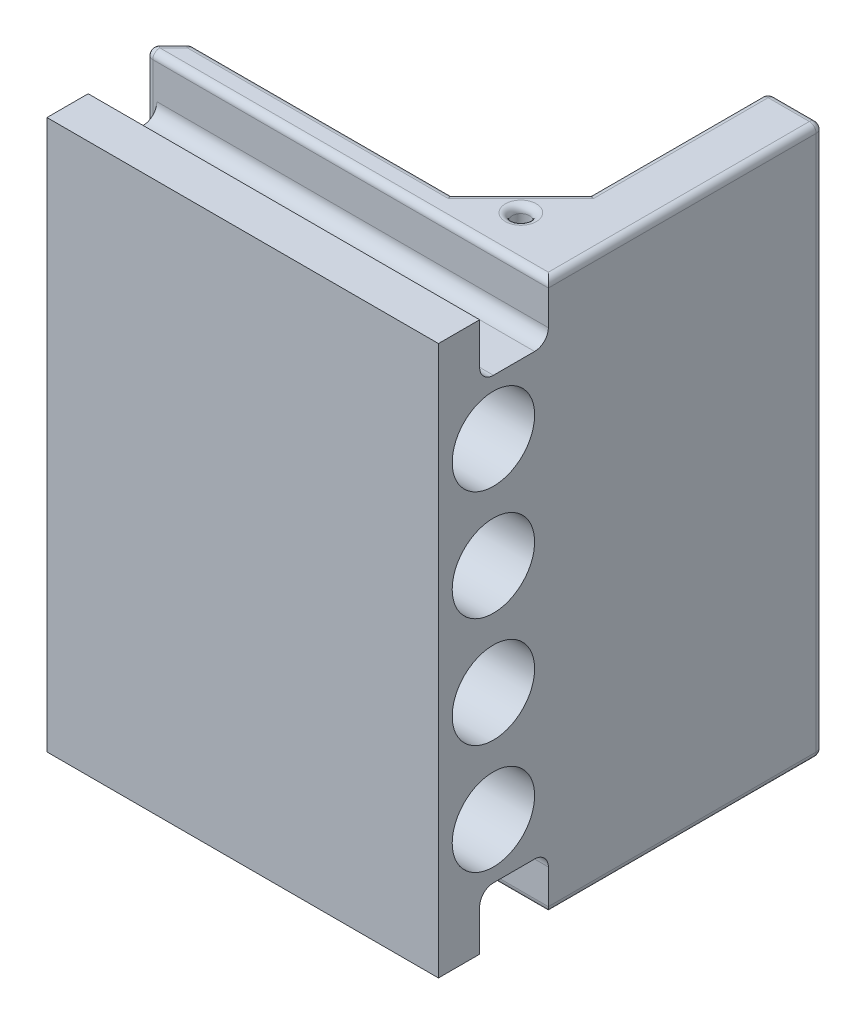
SolidWorks part; units mm, degrees
ref_plane "Front Plane" through (0, 0, 0) normal (0, 0, 1) x (1, 0, 0)
ref_plane "Top Plane" through (0, 0, 0) normal (0, 1, 0) x (1, 0, 0)
ref_plane "Right Plane" through (0, 0, 0) normal (1, 0, 0) x (0, 0, -1)
sketch "Sketch1" plane through (0, 0, 0) normal (0, 1, 0) x (1, 0, 0)
  line L0 (-17.3516, 20.3127) -> (-57.3516, -19.6873)
  line L1 (-17.3516, 20.3127) -> (2.6484, 20.3127)
  line L2 (-17.3516, 20.3127) -> (-17.3516, -19.6873)
  line L3 (-17.3516, -19.6873) -> (2.6484, -19.6873)
  line L4 (2.6484, 20.3127) -> (2.6484, -19.6873)
  line L5 (-57.3516, -19.6873) -> (-17.3516, -19.6873)
  dimension "D1" = 20
  dimension "D2" = 40
  dimension "D3" = 40
extrude "Boss-Extrude1" add sketch "Sketch1" against normal blind 80 contours L0 L5 L2 | L4 L1 L2 L3 region at (-30.685, 0, 6.3539) region at (-7.3516, 0, -0.3127)
sketch "Sketch8" plane through (2.6484, 0, 0) normal (1, 0, 0) x (0, 0, -1)
  line L0 (-19.6873, -80) -> (-19.6873, 0) construction
  line L14 (-19.6873, -8) -> (-35.6873, -8)
  line L15 (-19.6873, -8) -> (-19.6873, -72)
  line L16 (-19.6873, -72) -> (-35.6873, -72)
  line L17 (-35.6873, -8) -> (-35.6873, -72)
  dimension "D2" = 64
  dimension "D3" = 8
  dimension "D12" = 16
extrude "Boss-Extrude2" add sketch "Sketch8" against normal blind 57
sketch "Sketch12" plane through (0, -72, 0) normal (0, -1, 0) x (1, 0, 0)
  line L0 (2.6484, 35.6873) -> (2.6484, 19.6873) construction
  line L1 (-54.3516, 35.6873) -> (2.6484, 35.6873)
  line L2 (-54.3516, 35.6873) -> (-54.3516, 29.6873)
  line L3 (-54.3516, 29.6873) -> (2.6484, 29.6873)
  line L4 (2.6484, 35.6873) -> (2.6484, 29.6873)
  dimension "D1" = 6
sketch "Sketch10" plane through (2.6484, 0, 0) normal (1, 0, 0) x (0, 0, -1)
  line L8 (-27.6873, -8) -> (-27.6873, -72) construction
  line L9 (-19.6873, -8) -> (-35.6873, -8) construction
  line L10 (-35.6873, -72) -> (-19.6873, -72) construction
  circle A0 centre (-27.6873, -16) radius 6
  circle A4 centre (-27.6873, -32) radius 6
  circle A5 centre (-27.6873, -64) radius 6
  circle A6 centre (-27.6873, -48) radius 6
  dimension "D1" = 12
  dimension "D2" = 8
extrude "Cut-Extrude1" cut sketch "Sketch10" against normal blind 51
extrude "Boss-Extrude3" add sketch "Sketch12" along normal blind 8
sketch "Sketch14" plane through (0, -8, 0) normal (0, 1, 0) x (1, 0, 0)
  line L0 (2.6484, -19.6873) -> (2.6484, -35.6873) construction
  line L1 (-54.3516, -35.6873) -> (2.6484, -35.6873)
  line L2 (-54.3516, -35.6873) -> (-54.3516, -29.6873)
  line L3 (-54.3516, -29.6873) -> (2.6484, -29.6873)
  line L4 (2.6484, -35.6873) -> (2.6484, -29.6873)
  dimension "D1" = 6
extrude "Boss-Extrude4" add sketch "Sketch14" along normal blind 8
sketch "Sketch17" plane through (0, 0, -20.3127) normal (0, 0, -1) x (-1, 0, 0)
  line L1 (5.3516, 0) -> (53.3516, 0)
  line L2 (5.3516, 0) -> (5.3516, -80)
  line L3 (5.3516, -80) -> (53.3516, -80)
  line L4 (53.3516, 0) -> (53.3516, -80)
  line L6 (57.3516, -80) -> (57.3516, 0) construction
  line L7 (-2.6484, -80) -> (-2.6484, 0) construction
  line L8 (17.3516, 0) -> (57.3516, 0) construction
  line L9 (17.3516, -80) -> (57.3516, -80) construction
  dimension "D3" = 4
  dimension "D4" = 8
extrude "Cut-Extrude4" cut sketch "Sketch17" against normal blind 36
chamfer "Chamfer1" distance 10 angle 45 1 edges at (-5.3516, -40, 15.6873)
sketch "Sketch16" plane through (0, 0, 15.6873) normal (0, 0, -1) x (-1, 0, 0)
  line L0 (53.3516, -80) -> (53.3516, 0) construction
  line L1 (53.3516, -76) -> (5.3516, -76)
  line L2 (53.3516, -76) -> (53.3516, -4)
  line L3 (53.3516, -4) -> (5.3516, -4)
  line L4 (5.3516, -76) -> (5.3516, -4)
  line L5 (5.3516, 0) -> (5.3516, -80) construction
  line L6 (53.3516, 0) -> (15.3516, 0) construction
  line L7 (15.3516, -80) -> (53.3516, -80) construction
  dimension "D1" = 4
  dimension "D2" = 4
extrude "Cut-Extrude5" cut sketch "Sketch16" along normal blind 10
sketch "Sketch19" plane through (0, 0, 0) normal (0, 1, 0) x (1, 0, 0)
  line L0 (-15.3516, -15.6873) -> (2.6484, -15.6873) construction
  line L1 (-5.3516, -5.6873) -> (-15.3516, -15.6873) construction
  line L2 (2.6484, 20.3127) -> (2.6484, -19.6873) construction
  line L3 (-5.3516, -5.6873) -> (-5.3516, -19.6873) construction
  line L4 (-57.3516, -19.6873) -> (2.6484, -19.6873) construction
  line L5 (-10.3516, -10.6873) -> (-5.3516, -15.6873) construction
  circle A0 centre (-7.8516, -13.1873) radius 1.25
  dimension "D1" = 2.5
extrude "Cut-Extrude6" cut sketch "Sketch19" against normal through all
fillet "Fillet1" radius 2 4 edges at (-25.8516, -8, 19.6873) (-25.8516, -8, 29.6873) (-25.8516, -72, 19.6873) (-25.8516, -72, 29.6873)
fillet "Fillet2" radius 2 4 edges at (-48.3516, -48, 21.6873) (-48.3516, -64, 33.6873) (-48.3516, -32, 33.6873) (-48.3516, -16, 21.6873)
fillet "Fillet3" radius 1 7 edges at (-5.3516, -4, 10.6873) (-10.3516, -4, 15.6873) (-5.3516, -76, 10.6873) (-10.3516, -76, 15.6873) (-5.3516, -40, 15.6873) (-53.3516, -40, 15.6873) (-57.3516, -40, 19.6873)
fillet "Fillet4" radius 1 4 edges at (-7.8516, 0, 14.4373) (-6.6016, -4, 13.1873) (-7.8516, -76, 14.4373) (-7.8516, -80, 14.4373)
fillet "Fillet5" radius 1 20 edges at (-26.1445, 0, 19.6873) (-55.8613, 0, 19.07) (-54.6445, 0, 16.9802) (-53.3201, 0, 15.7634) (-26.1445, -80, 19.6873) (-55.8613, -80, 19.07) (-54.6445, -80, 16.9802) (-53.3201, -80, 15.7634) (-34.1445, 0, 15.6873) (-10.3516, 0, 10.6873) (-5.3516, 0, -7.3127) (-1.3516, 0, -20.3127) (2.6484, 0, -0.3127) (2.6484, -80, -0.3127) (2.6484, -40, -20.3127) (-5.3516, -40, -20.3127) (-1.3516, -80, -20.3127) (-5.3516, -80, -7.3127) (-10.3516, -80, 10.6873) (-34.1445, -80, 15.6873)
